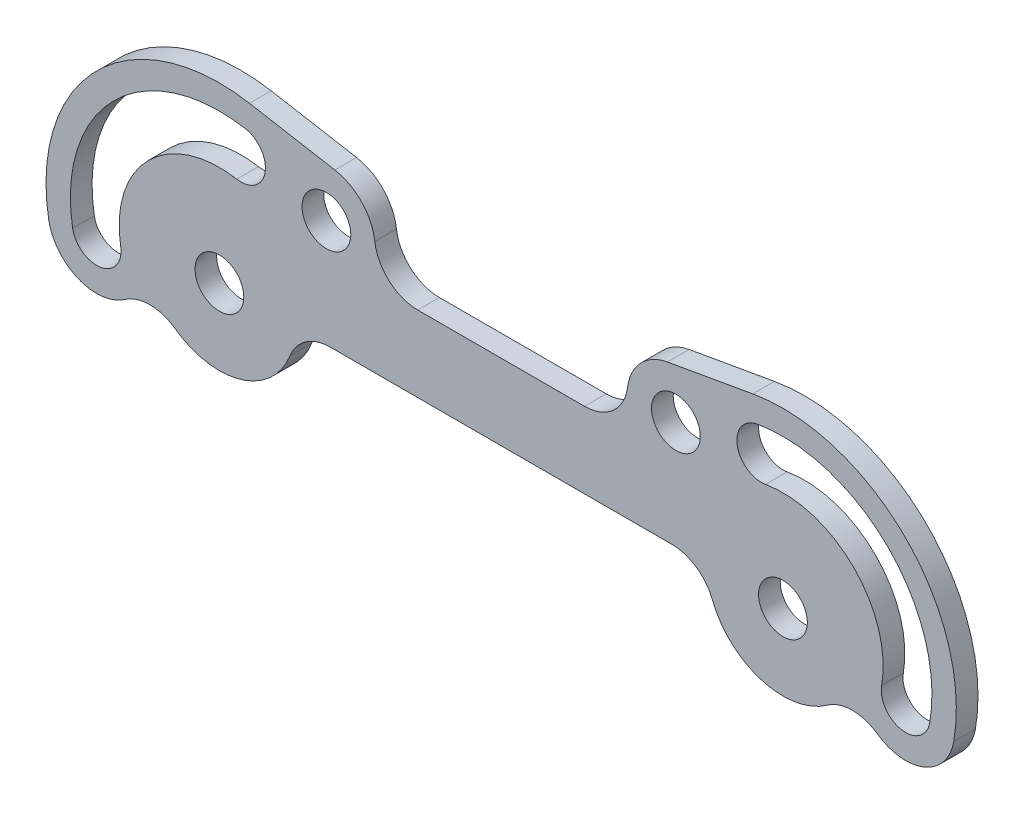
SolidWorks part; units mm, degrees
ref_plane "Front Plane" through (0, 0, 0) normal (0, 0, 1) x (1, 0, 0)
ref_plane "Top Plane" through (0, 0, 0) normal (0, 1, 0) x (1, 0, 0)
ref_plane "Right Plane" through (0, 0, 0) normal (1, 0, 0) x (0, 0, -1)
sketch "Sketch1" plane through (0, 0, 0) normal (0, 0, 1) x (1, 0, 0)
  line L0 (0, 0) -> (-20.6375, 0)
  line L1 (-20.6375, 0) -> (-20.6375, 5.5562) construction
  line L2 (-20.6375, 0) -> (-18.4322, 12.5071) construction
  line L3 (-20.6375, 0) -> (-26.1937, 0) construction
  line L4 (-20.6375, 0) -> (-33.1446, -2.2053) construction
  line L5 (-19.0524, 8.9894) -> (-12.7989, 7.8868) construction
  line L6 (-10.0921, 5.5562) -> (0, 5.5562)
  line L7 (0, 5.5562) -> (0, 0)
  line L8 (-12.1786, 11.4044) -> (-13.4191, 4.3692) construction
  line L9 (-18.4322, 12.5071) -> (-12.1786, 11.4044)
  line L10 (0, 5.5562) -> (0, -5.5619) construction
  circle A0 centre (-20.6375, 0) radius 1.7859
  circle A2 centre (-20.6375, 0) radius 9.1281 construction
  circle A3 centre (-20.6375, 0) radius 5.5562
  circle A4 centre (-19.0524, 8.9894) radius 1.7859
  circle A5 centre (-29.6269, -1.5851) radius 1.7859
  circle A7 centre (-12.7989, 7.8868) radius 1.7859
  circle A8 centre (-29.6269, -1.5851) radius 3.5719
  circle A9 centre (-19.0524, 8.9894) radius 3.5719
  circle A10 centre (-12.7989, 7.8868) radius 3.5719
  arc A11 (-19.3625, 7.2306) -> (-27.8681, -1.275) centre (-20.6375, 0) ccw
  arc A12 (-18.7423, 10.7483) -> (-31.3858, -1.8952) centre (-20.6375, 0) ccw
  arc A13 (-18.4322, 12.5071) -> (-33.1446, -2.2053) centre (-20.6375, 0) ccw
  point P29 (0, 0)
  point P30 (0, 0)
  dimension "D1" = 3.5719
  dimension "D5" = 11.1125
  dimension "D6" = 7.1437
  dimension "D2" = 20.6375
  dimension "D3" = 10
  dimension "D4" = 10
  dimension "D7" = 6.35
extrude "Boss-Extrude1" add sketch "Sketch1" along normal blind 1.5875 contours A3 A0 | A12 A8 A11 A5 | A9 A13 A8 A12 | A9 A11 A8 A3 | A12 A4 A11 A9 A10 | A9 A10 | A10 L9 A9 | A10 A9 A7 | A10 A9 A3 L0 L7 L6 region at (-8.0349, 2.8138, 0) region at (-20.1669, -5.3786, 0) region at (-24.8448, 4.2073, 0) region at (-21.0384, 6.1375, 0) region at (-26.1659, -1.2823, 0) region at (-13.5048, 4.4873, 0) region at (-15.9257, 8.4381, 0) region at (-28.504, 7.8665, 0) region at (-15.3989, 11.4257, 0)
fillet "Fillet1" radius 3.175 3 edges at (-26.1093, -0.9648, 0.7937) (-15.0813, 0, 0.7937) (-10.0921, 5.5562, 0.7937)
mirror "Mirror1" about plane through (0, 0, 1.5875) normal (1, 0, 0) of "Fillet1", "Boss-Extrude1"
